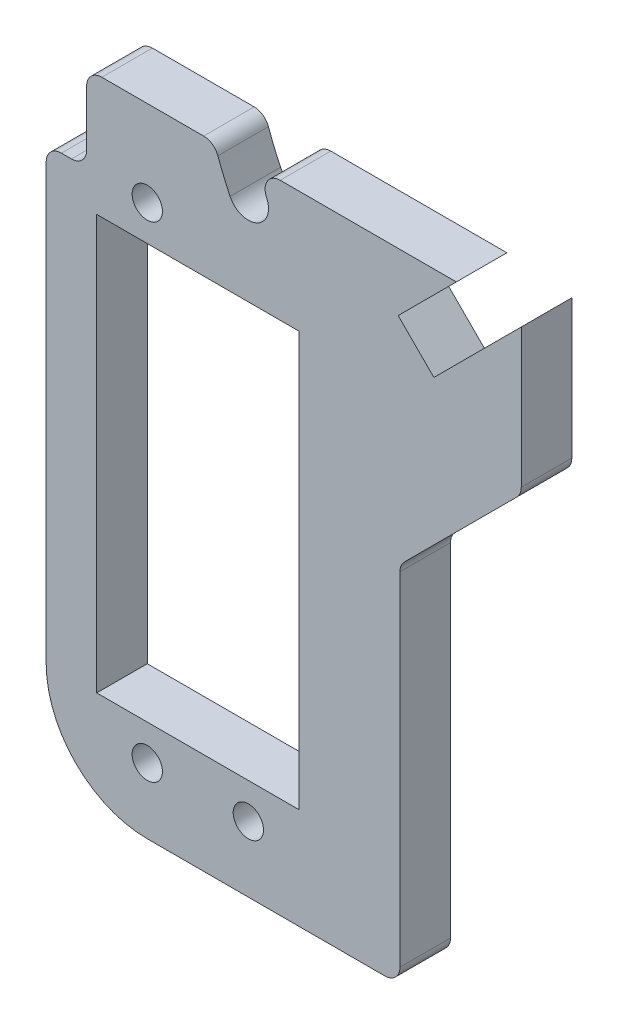
SolidWorks part; units mm, degrees
ref_plane "Plan de face" through (0, 0, 0) normal (0, 0, 1) x (1, 0, 0)
ref_plane "Plan de dessus" through (0, 0, 0) normal (0, 1, 0) x (1, 0, 0)
ref_plane "Plan de droite" through (0, 0, 0) normal (1, 0, 0) x (0, 0, -1)
sketch "Esquisse1" plane through (0, 0, 0) normal (0, 0, 1) x (1, 0, 0)
  line L0 (15, 10) -> (15, 51) construction
  line L1 (0, 0) -> (35, 0)
  line L2 (0, 0) -> (0, 54.5)
  line L3 (4, 63) -> (16.7463, 63)
  line L4 (47.6474, 63) -> (38.3549, 53.7075)
  line L5 (15, 51) -> (5, 51)
  line L6 (20.8844, 63) -> (47.6474, 63)
  line L7 (25, 10) -> (5, 10)
  line L8 (5, 51) -> (5, 10)
  line L9 (5, 30.5) -> (25, 30.5) construction
  line L10 (25, 10) -> (25, 51)
  line L11 (25, 51) -> (15, 51)
  line L12 (34.8194, 57.2431) -> (38.3549, 53.7075) construction
  line L13 (47, 48) -> (47, 63)
  line L14 (43.3047, 58.6573) -> (36.2336, 51.5862) construction
  line L15 (38.3549, 53.7075) -> (34.8194, 57.2431)
  line L16 (34.8194, 57.2431) -> (40.5763, 63)
  line L17 (47.6474, 63) -> (47, 63)
  line L18 (47.6474, 63) -> (20.8844, 63)
  line L19 (20.8844, 63) -> (40.5763, 63)
  line L20 (47, 48) -> (35, 36)
  line L21 (35, 36) -> (35, 0)
  line L22 (0, 54.5) -> (4, 54.5)
  line L23 (4, 63) -> (4, 54.5)
  circle A0 centre (10, 54.5) radius 1.5
  circle A1 centre (20, 54.5) radius 1.5 construction
  circle A2 centre (20, 6.5) radius 1.5
  circle A3 centre (10, 6.5) radius 1.5
  arc A4 (18.7561, 63) -> (19.9935, 60) centre (46.8198, 72.8198) ccw construction
  arc A5 (16.8013, 62.5331) -> (18.1889, 59.1376) centre (46.8198, 72.8198) ccw
  arc A6 (20.8844, 63) -> (21.798, 60.8624) centre (46.8198, 72.8198) ccw
  arc A7 (16.7463, 63) -> (16.8013, 62.5331) centre (18.7561, 63) ccw
  arc A8 (18.1889, 59.1376) -> (21.798, 60.8624) centre (19.9935, 60) ccw
  point P35 (14.7126, 61.0586)
  dimension "D6" = 3.5
  dimension "D8" = 3
  dimension "D14" = 2
  dimension "D15" = 27.7321
  dimension "D16" = 31.7321
  dimension "D20" = 29.7321
  dimension "D1" = 20
  dimension "D2" = 41
  dimension "D3" = 10
  dimension "D4" = 12
  dimension "D5" = 5
  dimension "D7" = 5
  dimension "D9" = 22
  dimension "D10" = 5
  dimension "D12" = 4
  dimension "D13" = 8.5
  dimension "D17" = 1.9548
  dimension "D18" = 10
  dimension "D19" = 15
  dimension "D21" = 3
extrude "Boss.-Extru.1" add sketch "Esquisse1" along normal blind 5 contours L17 L6 L4 L15 L16 L3 L2 L1 L13 L11 L10 L7 L8 L5 A0 A2 A3 region at (0.786, 27.25, 0)
fillet "Congé2" radius 10 1 edges at (0, 0, 2.5)
fillet "Congé4" radius 1.5 8 edges at (0, 54.5, 2.5) (4, 54.5, 2.5) (47, 48, 2.5) (35, 36, 2.5) (35, 0, 2.5) (20.8844, 63, 2.5) (16.7463, 63, 2.5) (4, 63, 2.5)
